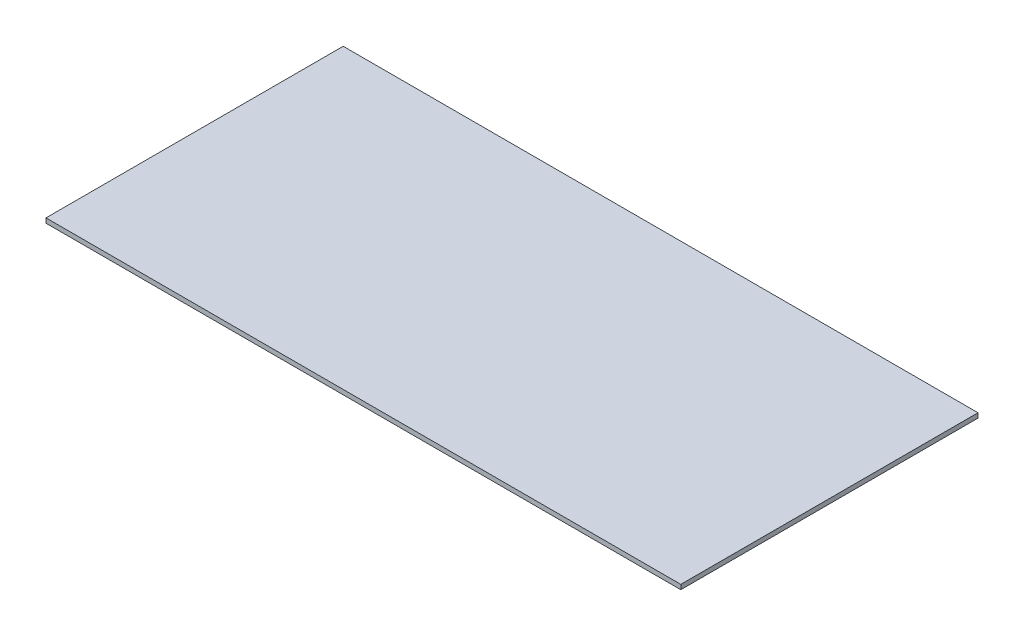
SolidWorks part; units mm, degrees
material "Mahogany"
ref_plane "Front Plane" through (0, 0, 0) normal (0, 0, 1) x (1, 0, 0)
ref_plane "Top Plane" through (0, 0, 0) normal (0, 1, 0) x (1, 0, 0)
ref_plane "Right Plane" through (0, 0, 0) normal (1, 0, 0) x (0, 0, -1)
sketch "Sketch1" plane through (0, 0, 0) normal (0, 1, 0) x (1, 0, 0)
  line L1 (865, -405) -> (-865, -405)
  line L2 (865, -405) -> (865, 405)
  line L3 (865, 405) -> (-865, 405)
  line L4 (-865, -405) -> (-865, 405)
  line L5 (865, -405) -> (-865, 405) construction
  line L6 (865, 405) -> (-865, -405) construction
  point P0 (0, 0)
  dimension "D1" = 1730
  dimension "D2" = 810
extrude "Boss-Extrude1" add sketch "Sketch1" along normal blind 12.7
equation "\"W\"= 1700"
equation "\"L\"= 780"
equation "\"H\"= 780"
equation "\"ARM_BOLT_SPACING\"= 166"
equation "\"ARM_TO_WALL\"= 200"
equation "\"D1@Sketch1\"=\"W\"+30"
equation "\"D2@Sketch1\"=\"L\"+30"
